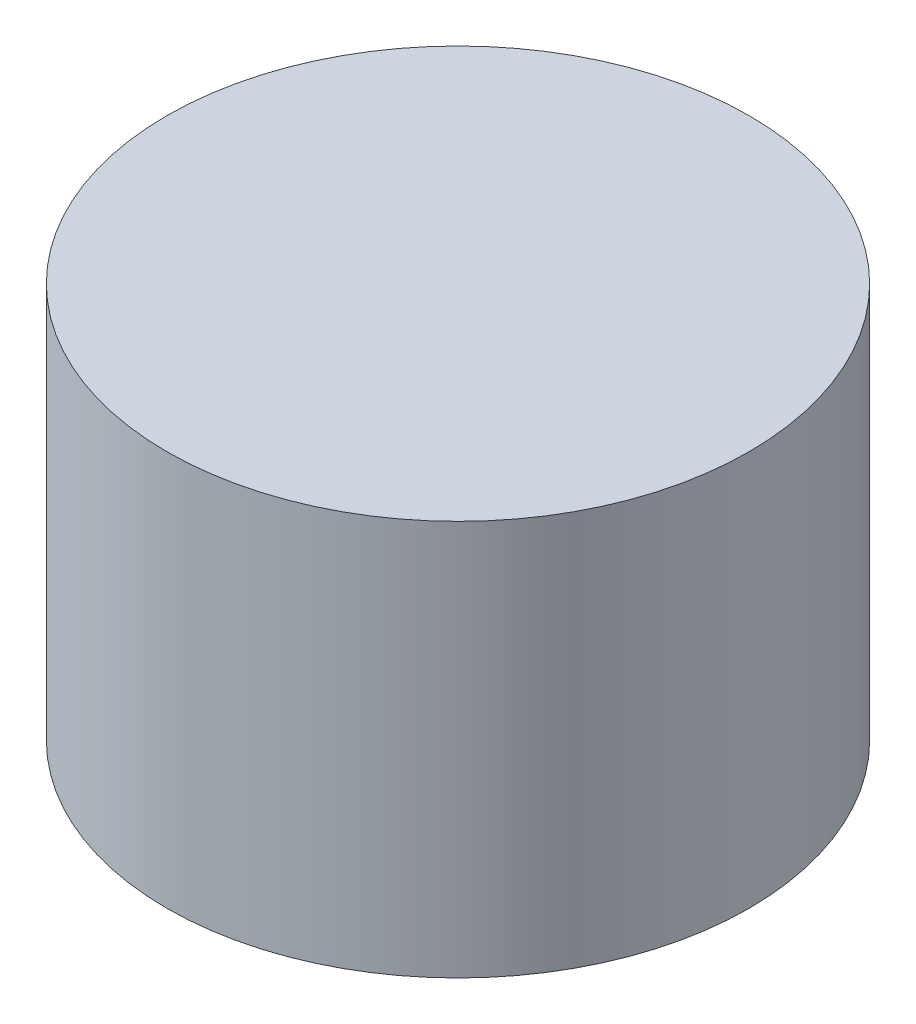
SolidWorks part; units mm, degrees
ref_plane "Front Plane" through (0, 0, 0) normal (0, 0, 1) x (1, 0, 0)
ref_plane "Top Plane" through (0, 0, 0) normal (0, 1, 0) x (1, 0, 0)
ref_plane "Right Plane" through (0, 0, 0) normal (1, 0, 0) x (0, 0, -1)
sketch "Sketch1" plane through (0, 0, 0) normal (0, 0, 1) x (1, 0, 0)
  line L0 (26.5, 36) -> (26.5, 0)
  line L1 (0, 31) -> (0, 0) construction
  line L5 (26.5, 0) -> (21.5, 0) construction
  line L6 (0, 31) -> (26.5, 31) construction
  line L7 (0, 0) -> (21.5, 0) construction
  line L12 (26.5, 36) -> (0, 36)
  line L13 (0, 36) -> (0, 31)
  line L14 (21.5, 0) -> (21.5, 36) construction
  line L17 (21.5, 0) -> (23, 0)
  line L18 (25, 0) -> (26.5, 0)
  arc A1 (25, 0) -> (23, 0) centre (24, 0) ccw
  conic Q0 (0, 31) -> (21.5, 0) control (21.5, 31) rho 0.3
  dimension "o ring radius" = 1
  dimension "Foam Thickness" = 5
  dimension "Egg Height/2" = 31
  dimension "egg max radius" = 21.5
revolve "Revolve1" add sketch "Sketch1" angle 360 about L1
